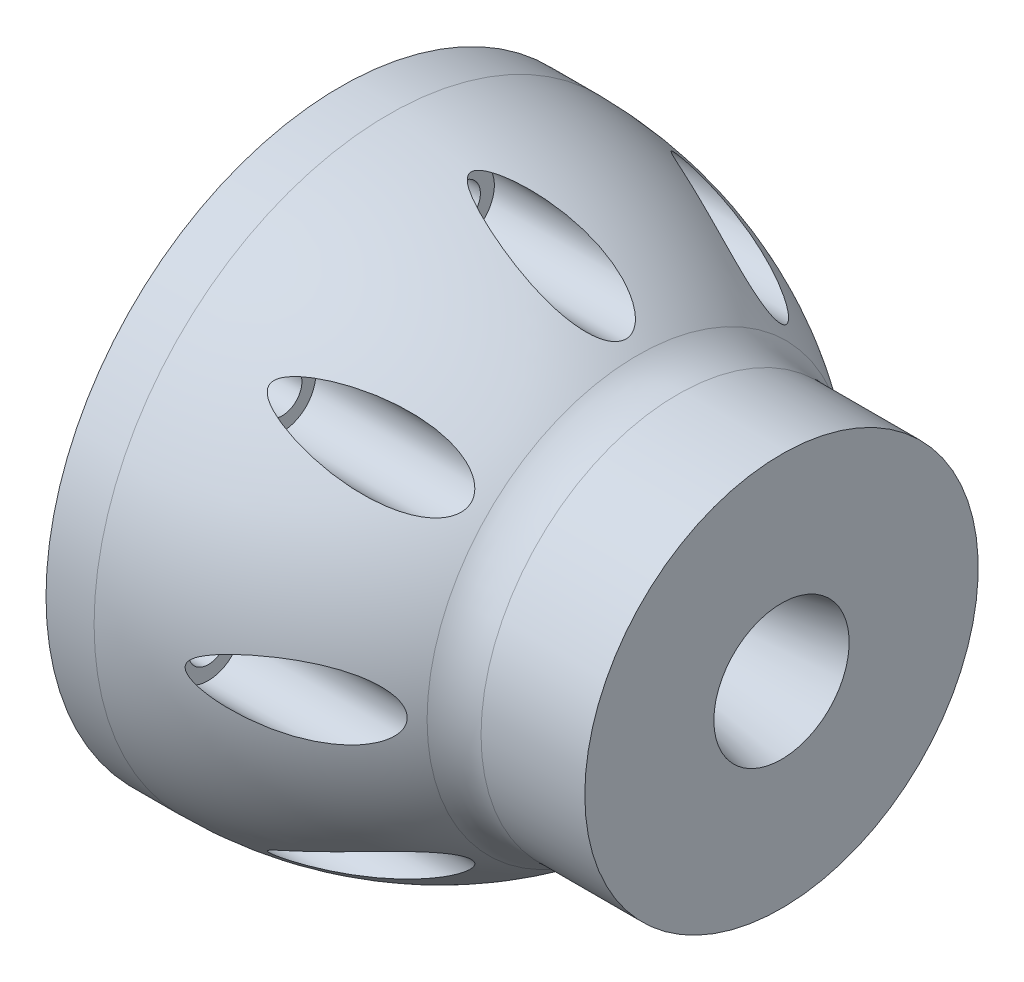
SolidWorks part; units mm, degrees
ref_plane "Front Plane" through (0, 0, 0) normal (0, 0, 1) x (1, 0, 0)
ref_plane "Top Plane" through (0, 0, 0) normal (0, 1, 0) x (1, 0, 0)
ref_plane "Right Plane" through (0, 0, 0) normal (1, 0, 0) x (0, 0, -1)
sketch "Model" plane through (0, 0, 0) normal (0, 0, 1) x (1, 0, 0)
  line L0 (0, 19.051) -> (31.9536, 19.051)
  line L1 (38.3809, 16.3887) -> (49.0299, 5.7397)
  line L2 (0, 0) -> (61.8717, 0) construction
  arc A0 (38.3809, 16.3887) -> (31.9536, 19.051) centre (31.9536, 9.9615) ccw
  arc A1 (49.0299, 5.7397) -> (50.8, 5.0065) centre (50.8, 7.5097) ccw
  arc A2 (50.8, 5.0065) -> (51.2904, 5.055) centre (50.8, 7.5097) ccw
  spline S0 degree 2 poles (51.2904, 5.055) (61.5184, 7.0984) (61.8717, 7.148) knots 0 0 0 1 1 1
  text T0 "Vortex_Chamber_Cold_Wall" font "SWTXT" height 5
sketch "Sketch2" plane through (0, 0, 0) normal (0, 0, 1) x (1, 0, 0)
  line L0 (61.8717, 7.148) -> (51.2904, 5.055)
  line L1 (49.0299, 5.7397) -> (38.3809, 16.3887)
  line L2 (31.9536, 19.051) -> (25.6036, 19.051)
  line L3 (0, 19.051) -> (31.9536, 19.051) construction
  line L4 (25.6036, 19.051) -> (25.6036, 22.225)
  line L5 (0, 0) -> (61.8717, 0) construction
  line L6 (25.6036, 22.225) -> (15.2714, 22.225)
  line L7 (15.2714, 22.225) -> (15.2714, 31.115)
  line L8 (15.2714, 31.115) -> (20.3519, 31.115)
  line L9 (50.9079, 20.7844) -> (61.8717, 20.7844)
  line L10 (61.8717, 20.7844) -> (61.8717, 7.148)
  arc A0 (51.2904, 5.055) -> (50.8, 5.0065) centre (50.7951, 7.5588) cw
  arc A1 (50.8, 5.0065) -> (49.0299, 5.7397) centre (50.7953, 7.4983) cw
  arc A2 (38.3809, 16.3887) -> (31.9536, 19.051) centre (31.9536, 9.9614) ccw
  arc A3 (20.3519, 31.115) -> (46.6468, 22.225) centre (20.3519, -12.2178) cw
  arc A4 (46.6468, 22.225) -> (50.9079, 20.7844) centre (50.9079, 27.8064) ccw
  point P21 (15.2714, 26.67)
  point P29 (41.1566, 25.4031)
  point P31 (50.307, 23.0502)
  point P32 (41.2438, 25.4903)
  point P33 (52.0499, 20.7844)
  point P34 (43.5096, 24.2702)
  point P35 (46.6468, 22.225)
  dimension "D1" = 6.35
  dimension "D2" = 22.225
  dimension "D3" = 26.67
revolve "Revolve1" add sketch "Sketch2" angle 360 about L2
sketch "Sketch3" plane through (15.2714, 0, 0) normal (-1, 0, 0) x (0, 0, 1)
  line L0 (0, 22.225) -> (0, 31.115) construction
  circle A0 centre (0, 26.67) radius 3.556
  circle A1 centre (0, 0) radius 22.225 construction
  circle A2 centre (0, 0) radius 22.225 construction
  circle A3 centre (0, 0) radius 31.115 construction
  point P11 (0, 26.67)
  dimension "D1" = 7.112
extrude "Cut-Extrude1" cut sketch "Sketch3" against normal up to surface (46.6004 mm away) from offset 12.7 up to face at (61.8717, 0, 20.7844) offset against normal yes
sketch "Sketch4" plane through (27.9714, 0, 0) normal (1, 0, 0) x (0, 0, -1)
  circle A0 centre (0, 26.67) radius 2.0828
  dimension "D1" = 4.1656
extrude "Cut-Extrude2" cut sketch "Sketch4" against normal up to surface (12.7 mm away) up to face at (15.2714, 0, 22.225)
pattern_circular "CirPattern1" count 8 over 360 about axis through (0, 0, 0) along (1, 0, 0) of "Cut-Extrude2", "Cut-Extrude1"
